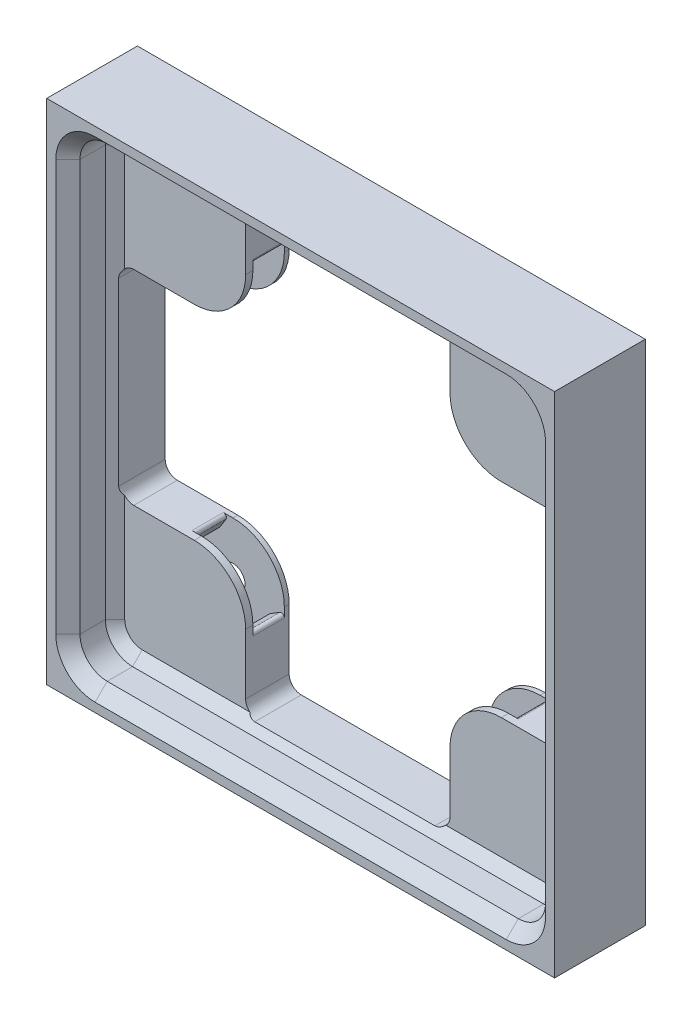
SolidWorks part; units mm, degrees
ref_plane "Front Plane" through (0, 0, 0) normal (0, 0, 1) x (1, 0, 0)
ref_plane "Top Plane" through (0, 0, 0) normal (0, 1, 0) x (1, 0, 0)
ref_plane "Right Plane" through (0, 0, 0) normal (1, 0, 0) x (0, 0, -1)
sketch "Sketch1" plane through (0, 0, 0) normal (0, 0, 1) x (1, 0, 0)
  line L0 (-21, 21) -> (0, 0) construction
  line L1 (-21, 0) -> (-18.7, 0)
  line L2 (-21, 0) -> (-21, 21)
  line L3 (-21, 21) -> (0, 21)
  line L5 (-13.7666, 9.63) -> (-9.63, 13.7666) construction
  line L6 (-10.4019, 14.9981) -> (-8.45, 13.0462) construction
  line L7 (-14.9981, 10.4019) -> (-13.0462, 8.45) construction
  line L8 (-13.4917, 8.45) -> (-18.7, 8.45)
  line L9 (-8.45, 13.4917) -> (-8.45, 18.7)
  line L10 (-9.63, 13.7666) -> (-8.8303, 13.2783)
  line L11 (-13.7666, 9.63) -> (-13.2783, 8.8303)
  line L12 (0, 18.7) -> (0, 21)
  line L13 (-8.45, 18.7) -> (0, 18.7)
  line L16 (-18.7, 0) -> (-18.7, 8.45)
  line L17 (-18.7, 18.7) -> (-2.3, 18.7) construction
  line L18 (-18.7, 2.3) -> (-18.7, 18.7) construction
  line L19 (-2.3, 2.3) -> (-2.3, 18.7) construction
  line L20 (-18.7, 2.3) -> (-2.3, 2.3) construction
  line L21 (0, 0) -> (0, 21) construction
  line L22 (-21, 0) -> (0, 0) construction
  arc A0 (-9.63, 13.7666) -> (-13.7666, 9.63) centre (-12.7, 12.7) ccw
  arc A2 (-13.4917, 8.45) -> (-13.2783, 8.8303) centre (-13.4917, 8.7) ccw
  arc A3 (-8.45, 13.4917) -> (-8.8303, 13.2783) centre (-8.7, 13.4917) cw
  circle A4 centre (-12.7, 12.7) radius 4.25 construction
  point P11 (-11.6983, 11.6983)
  dimension "D3" = 6.5
  dimension "D2" = 0.25
  dimension "D8" = 8.5
  dimension "D1" = 21
  dimension "D4" = 8.3
  dimension "D5" = 8.3
  dimension "D6" = 5.85
  dimension "D7" = 2.3
extrude "Magnet Slot" add sketch "Sketch1" along normal blind 2.6
sketch "Sketch2" plane through (0, 0, 2.6) normal (0, 0, 1) x (1, 0, 0)
  line L0 (-8.8303, 13.2783) -> (-9.63, 13.7666)
  line L2 (-13.7666, 9.63) -> (-13.2783, 8.8303)
  line L4 (-13.4917, 8.45) -> (-18.7, 8.45)
  line L5 (-12.7, 8.45) -> (-18.7, 8.45)
  line L6 (-18.7, 8.45) -> (-18.7, 0)
  line L7 (-18.7, 8.45) -> (-18.7, 0)
  line L8 (-18.7, 0) -> (-21, 0)
  line L9 (-18.7, 0) -> (-21, 0)
  line L10 (-21, 0) -> (-21, 21)
  line L11 (-21, 0) -> (-21, 21)
  line L12 (-21, 21) -> (0, 21)
  line L13 (-21, 21) -> (0, 21)
  line L14 (0, 21) -> (0, 18.7)
  line L15 (0, 21) -> (0, 18.7)
  line L16 (0, 18.7) -> (-8.45, 18.7)
  line L17 (0, 18.7) -> (-8.45, 18.7)
  line L18 (-8.45, 18.7) -> (-8.45, 13.4917)
  line L19 (-8.45, 18.7) -> (-8.45, 12.7)
  arc A0 (-9.63, 13.7666) -> (-13.7666, 9.63) centre (-12.7, 12.7) ccw
  arc A2 (-13.4917, 8.45) -> (-13.2783, 8.8303) centre (-13.4917, 8.7) ccw
  arc A4 (-8.8303, 13.2783) -> (-8.45, 13.4917) centre (-8.7, 13.4917) ccw
  arc A6 (-12.7, 8.45) -> (-8.45, 12.7) centre (-12.7, 12.7) ccw
  dimension "D1" = 8.5
extrude "Magnet Topper" add sketch "Sketch2" along normal blind 0.6
sketch "Sketch3" plane through (0, 0, 0) normal (0, 0, -1) x (-1, 0, 0)
  line L8 (18.7, 8.45) -> (18.7, 0)
  line L9 (12.7, 8.45) -> (18.7, 8.45)
  line L10 (8.45, 18.7) -> (8.45, 12.7)
  line L11 (0, 18.7) -> (8.45, 18.7)
  line L12 (0, 21) -> (0, 18.7)
  line L13 (21, 21) -> (0, 21)
  line L14 (21, 0) -> (21, 21)
  line L15 (18.7, 0) -> (21, 0)
  line L16 (18.7, 8.45) -> (18.7, 0)
  line L17 (12.7, 8.45) -> (18.7, 8.45)
  line L18 (8.45, 18.7) -> (8.45, 12.7)
  line L19 (0, 18.7) -> (8.45, 18.7)
  line L20 (0, 21) -> (0, 18.7)
  line L21 (21, 21) -> (0, 21)
  line L22 (21, 0) -> (21, 21)
  line L23 (18.7, 0) -> (21, 0)
  arc A1 (8.45, 12.7) -> (12.7, 8.45) centre (12.7, 12.7) ccw
  arc A2 (8.45, 12.7) -> (12.7, 8.45) centre (12.7, 12.7) ccw
  dimension "D1" = 0
extrude "Bottom" add sketch "Sketch3" along normal blind 0.4
sketch "Sketch4" plane through (0, 0, -0.4) normal (0, 0, -1) x (-1, 0, 0)
  line L0 (12.7, 12.7) -> (21, 21) construction
  line L1 (21, 21) -> (0, 21) construction
  line L2 (21, 0) -> (21, 21) construction
  line L3 (12.7, 12.7) -> (16.2355, 16.2355) construction
  line L4 (11.9929, 13.4071) -> (15.5284, 16.9426)
  line L5 (13.4071, 11.9929) -> (16.9426, 15.5284)
  arc A0 (13.7666, 9.63) -> (9.63, 13.7666) centre (12.7, 12.7) ccw construction
  arc A1 (13.7666, 9.63) -> (9.63, 13.7666) centre (12.7, 12.7) ccw construction
  arc A2 (11.9929, 13.4071) -> (13.4071, 11.9929) centre (12.7, 12.7) ccw
  arc A3 (16.9426, 15.5284) -> (15.5284, 16.9426) centre (16.2355, 16.2355) ccw
  point P3 (14.4678, 14.4678)
  dimension "D1" = 5
extrude "Cut-Extrude1" cut sketch "Sketch4" against normal up to surface (3 mm away) up to face at (-11.3553, 11.3553, 2.6)
fillet "Fillet1" radius 1 2 edges at (-8.45, 18.7, 1.4) (-18.7, 8.45, 1.4)
sketch "Sketch5" plane through (0, 0, 3.2) normal (0, 0, 1) x (1, 0, 0)
  line L0 (0, 21) -> (-17.25, 21)
  line L1 (-21, 17.25) -> (-21, 0)
  line L2 (0, 19.25) -> (-17, 19.25)
  line L3 (-19.25, 17) -> (-19.25, 0)
  line L4 (-21, 0) -> (-19.25, 0)
  line L5 (0, 21) -> (0, 19.25)
  line L6 (0, 19.25) -> (-19.25, 19.25) construction
  line L7 (-19.25, 19.25) -> (-19.25, 0) construction
  line L8 (0, 21) -> (-21, 21) construction
  line L9 (-21, 21) -> (-21, 0) construction
  line L10 (-17.25, 21) -> (-21, 21)
  line L11 (-21, 21) -> (-21, 17.25)
  arc A0 (-17, 19.25) -> (-19.25, 17) centre (-17, 17) ccw
  point P15 (-21, 21)
  dimension "D2" = 2.25
  dimension "D1" = 1.75
extrude "Boss-Extrude1" add sketch "Sketch5" along normal blind 3.9
chamfer "Chamfer1" distance 0.8 angle 45 3 edges at (-19.25, 8.5, 3.2) (-18.591, 18.591, 3.2) (-8.5, 19.25, 3.2)
chamfer "Chamfer2" distance 1 angle 45 3 edges at (-8.5, 19.25, 7.1) (-18.591, 18.591, 7.1) (-19.25, 8.5, 7.1)
ref_axis "Center Axis" through (0, 0, 0) along (0, 0, 1)
pattern_circular "CirPattern1" count 4 over 360 about axis through (0, 0, 0) along (0, 0, 1) of bodies 105
combine bodies "Combine1" bodies to combine 105 108 106 107
